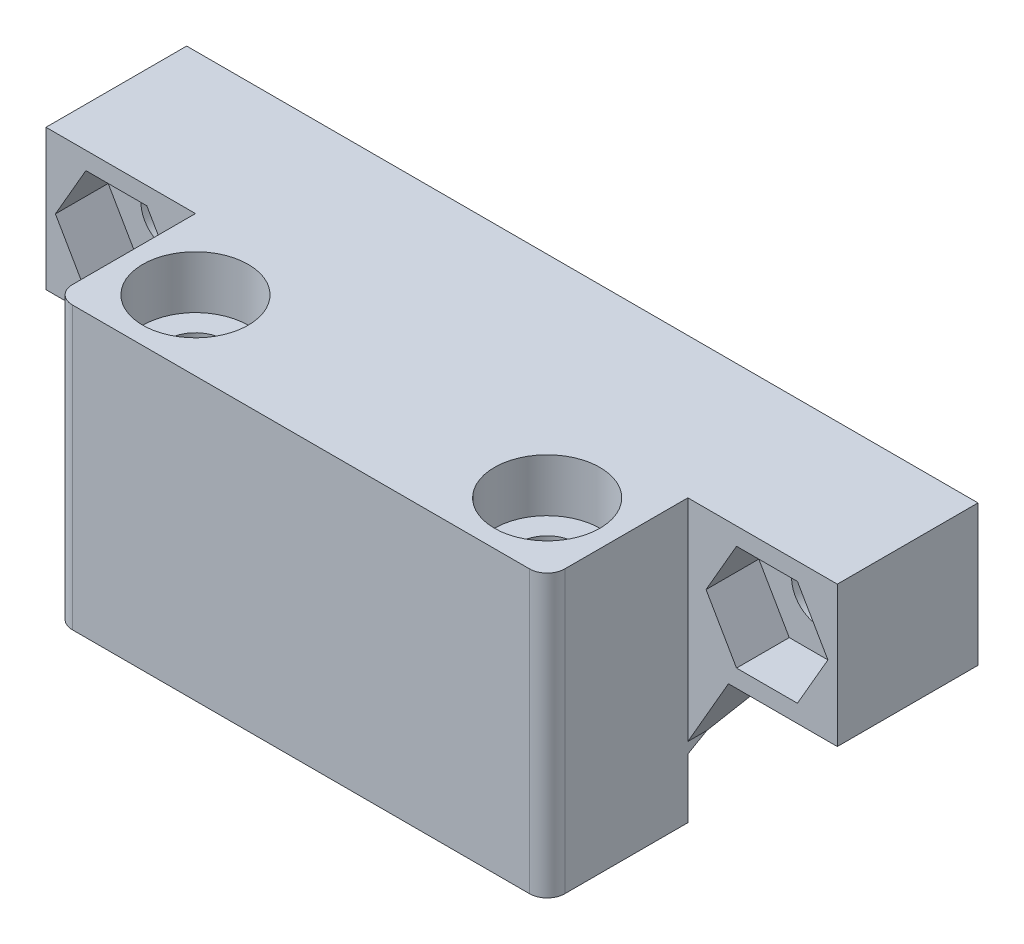
SolidWorks part; units mm, degrees
ref_plane "正面" through (0, 0, 0) normal (0, 0, 1) x (1, 0, 0)
ref_plane "平面" through (0, 0, 0) normal (0, 1, 0) x (1, 0, 0)
ref_plane "右側面" through (0, 0, 0) normal (1, 0, 0) x (0, 0, -1)
sketch "ｽｹｯﾁ1" plane through (0, 0, 0) normal (0, 0, 1) x (1, 0, 0)
  line L0 (0, 0) -> (-18.5, 0) construction
  line L1 (0, 4) -> (0, 0) construction
  line L3 (-22.5, 4) -> (22.5, 4)
  line L4 (-22.5, 4) -> (-22.5, -4)
  line L5 (-22.5, -4) -> (22.5, -4)
  line L6 (22.5, 4) -> (22.5, -4)
  line L7 (-22.5, 4) -> (22.5, -4) construction
  line L8 (-22.5, -4) -> (22.5, 4) construction
  circle A0 centre (-18.5, 0) radius 1.6
  circle A1 centre (18.5, 0) radius 1.6
  point P11 (0, 4)
  dimension "D1" = 3.2
  dimension "D2" = 18.5
  dimension "D3" = 45
  dimension "D4" = 8
extrude "ﾎﾞｽ - 押し出し1" add sketch "ｽｹｯﾁ1" along normal blind 8
sketch "ｽｹｯﾁ2" plane through (0, -4, 0) normal (0, -1, 0) x (1, 0, 0)
  line L0 (-22.5, 8) -> (22.5, 8) construction
  line L1 (-14, 16) -> (14, 16)
  line L2 (-14, 16) -> (-14, 8)
  line L3 (-14, 8) -> (14, 8)
  line L4 (14, 16) -> (14, 8)
  line L5 (-14, 16) -> (14, 8) construction
  line L6 (-14, 8) -> (14, 16) construction
  line L7 (-10, 12) -> (10, 12) construction
  line L8 (0, 12) -> (0, 0) construction
  circle A0 centre (-10, 12) radius 1.6
  circle A1 centre (10, 12) radius 1.6
  point P0 (0, 12)
  point P9 (0, 12)
  dimension "D1" = 20
  dimension "D2" = 3.2
  dimension "D3" = 28
  dimension "D4" = 8
extrude "ﾎﾞｽ - 押し出し2" add sketch "ｽｹｯﾁ2" along normal blind 8 and the other way blind 8
sketch "ｽｹｯﾁ3" plane through (0, 0, 8) normal (0, 0, 1) x (1, 0, 0)
  line L0 (18.5, 0) -> (15.0359, 0) construction
  line L1 (15.0359, 0) -> (16.7679, -3)
  line L2 (16.7679, -3) -> (20.2321, -3)
  line L3 (20.2321, -3) -> (21.9641, 0)
  line L4 (21.9641, 0) -> (20.2321, 3)
  line L5 (20.2321, 3) -> (16.7679, 3)
  line L6 (16.7679, 3) -> (15.0359, 0)
  line L7 (0, 4) -> (0, -12) construction
  line L8 (14, 4) -> (-14, 4) construction
  line L9 (14, -12) -> (-14, -12) construction
  line L10 (-18.5, 0) -> (-15.0359, 0) construction
  line L11 (-16.7679, 3) -> (-15.0359, 0)
  line L12 (-20.2321, 3) -> (-16.7679, 3)
  line L13 (-21.9641, 0) -> (-20.2321, 3)
  line L14 (-20.2321, -3) -> (-21.9641, 0)
  line L15 (-16.7679, -3) -> (-20.2321, -3)
  line L16 (-15.0359, 0) -> (-16.7679, -3)
  circle A0 centre (18.5, 0) radius 3 construction
  circle A1 centre (-18.5, 0) radius 3 construction
  dimension "D1" = 6
extrude "ｶｯﾄ - 押し出し1" cut sketch "ｽｹｯﾁ3" against normal blind 3
sketch "ｽｹｯﾁ4" plane through (0, 4, 0) normal (0, 1, 0) x (1, 0, 0)
  line L0 (0, 0) -> (0, -16) construction
  line L1 (22.5, 0) -> (-22.5, 0) construction
  line L2 (14, -16) -> (-14, -16) construction
  circle A0 centre (10, -12) radius 3
  circle A1 centre (-10, -12) radius 3
  dimension "D1" = 6
extrude "ｶｯﾄ - 押し出し2" cut sketch "ｽｹｯﾁ4" against normal blind 3
fillet "ﾌｨﾚｯﾄ1" radius 1 2 edges at (-14, -4, 16) (14, -4, 16)
chamfer "面取り1" distance 8 angle 30 1 edges at (0, -4, 8) first distance on face at (0, -4, 5.3333)
chamfer "面取り2" distance 4 angle 30 2 edges at (14, -4, 4) (-14, -4, 4) first distance on face at (14, -4.6598, 8.8571) first distance on face at (-14, -4.6598, 8.8571)
